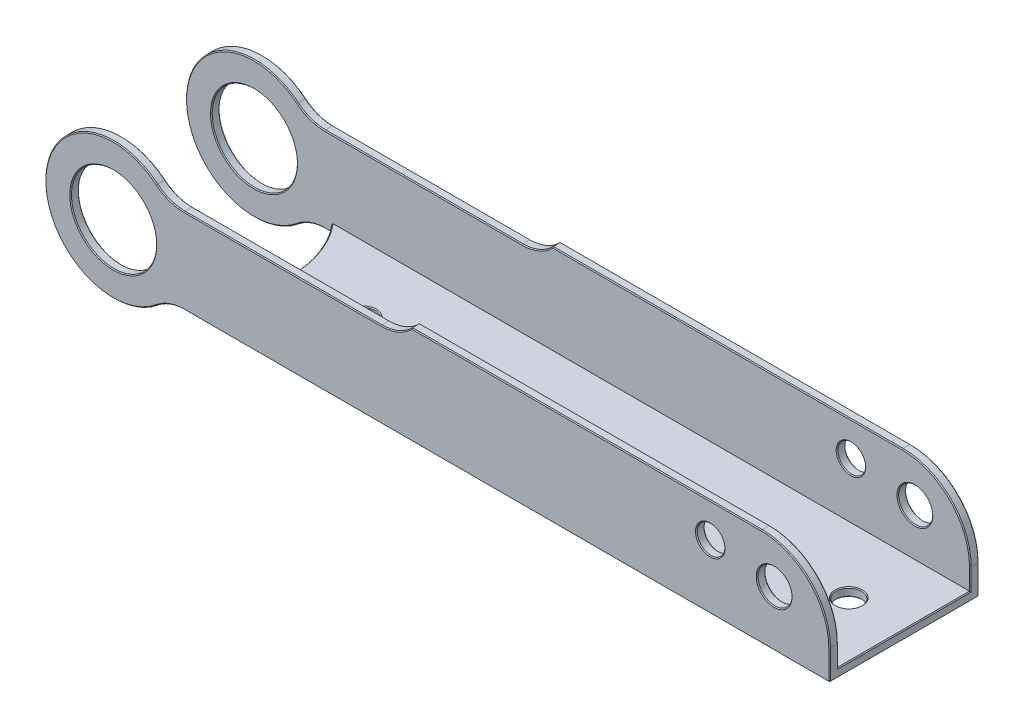
SolidWorks part; units mm, degrees
ref_plane "正面" through (0, 0, 0) normal (0, 0, 1) x (1, 0, 0)
ref_plane "平面" through (0, 0, 0) normal (0, 1, 0) x (1, 0, 0)
ref_plane "右側面" through (0, 0, 0) normal (1, 0, 0) x (0, 0, -1)
sketch "ArmA-L" plane through (0, 0, 0) normal (0, 0, 1) x (1, 0, 0)
  line L1 (12.49, 10) -> (70, 10)
  line L3 (12.49, -10) -> (168, -10)
  line L6 (70, 10) -> (70, 13)
  line L7 (70, 13) -> (168, 13)
  line L8 (168, -10) -> (168, 13)
  arc A0 (12.49, 10) -> (12.49, -10) centre (0, 0) ccw
  point P6 (70, 11.5)
  dimension "D2" = 32
  dimension "D1" = 70
  dimension "D3" = 168
  dimension "D4" = 3
  dimension "D5" = 10
extrude "ArmA-W" add sketch "ArmA-L" along normal mid plane 35
fillet "ﾌｨﾚｯﾄ1" radius 16 1 edges at (168, 13, 0)
fillet "ﾌｨﾚｯﾄ2" radius 10 3 edges at (12.49, -10, 0) (12.49, 10, 0) (70, 10, 0)
sketch "ｽｹｯﾁ2" plane through (0, 0, 17.5) normal (0, 0, 1) x (1, 0, 0)
  circle A0 centre (0, 0) radius 10
  dimension "D1" = 20
extrude "ｶｯﾄ - 押し出し1" cut sketch "ｽｹｯﾁ2" against normal through all
sketch "ｽｹｯﾁ3" plane through (0, 0, 0) normal (0, 1, 0) x (1, 0, 0)
  line L5 (-16, 15.5) -> (-16, -15.5)
  line L6 (-16, -15.5) -> (18.3235, -15.5)
  line L7 (-16, 15.5) -> (18.3235, 15.5)
  line L8 (-16, -17.5) -> (10.2235, -17.5) construction
  arc A0 (18.3235, 15.5) -> (18.3235, -15.5) centre (0, 0) cw
  point P10 (-16, 0)
  dimension "D3" = 24
  dimension "D1" = 2
extrude "ｶｯﾄ - 押し出し2" cut sketch "ｽｹｯﾁ3" against normal through all both and the other way through all
sketch "ArmA-t" plane through (0, 0, 0) normal (1, 0, 0) x (0, 0, -1)
  line L0 (-17.5, 13) -> (17.5, 13) construction
  line L1 (-15.5, -8) -> (15.5, -8)
  line L2 (-15.5, -8) -> (-15.5, 13)
  line L3 (-15.5, 13) -> (15.5, 13)
  line L4 (15.5, -8) -> (15.5, 13)
  line L5 (-17.5, -10) -> (17.5, -10) construction
  line L6 (15.5, 16) -> (15.5, -16) construction
  line L7 (-15.5, -16) -> (-15.5, 16) construction
  dimension "D1" = 2
extrude "ｶｯﾄ - 押し出し3" cut sketch "ArmA-t" along normal through all
sketch "ｽｹｯﾁ5" plane through (0, 0, 17.5) normal (0, 0, 1) x (1, 0, 0)
  line L0 (16.6132, -10) -> (168, -10) construction
  line L2 (168, -10) -> (168, -3) construction
  circle A0 centre (155, 3) radius 4
  circle A1 centre (140, 5) radius 3.25
  dimension "D1" = 8
  dimension "D2" = 6.5
  dimension "D4" = 15
  dimension "D3" = 13
  dimension "D5" = 13
  dimension "D6" = 28
extrude "ｶｯﾄ - 押し出し4" cut sketch "ｽｹｯﾁ5" against normal through all
sketch "ｽｹｯﾁ6" plane through (0, -10, 0) normal (0, -1, 0) x (1, 0, 0)
  line L0 (168, 17.5) -> (168, -17.5) construction
  circle A0 centre (155, 0) radius 3
  circle A1 centre (41, 0) radius 3
  dimension "D1" = 6
  dimension "D2" = 6
  dimension "D3" = 13
  dimension "D4" = 127
extrude "ｶｯﾄ - 押し出し5" cut sketch "ｽｹｯﾁ6" against normal up to next
chamfer "面取り1" distance 0.2 angle 45 56 edges at (155, -10, -3) (155, -8, 3) (41, -10, -3) (41, -8, 3) (168, -8, 0) (168, -10, 0) (159, 3, 15.5) (159, 3, 17.5) (143.25, 5, 15.5) (143.25, 5, 17.5) (151, 3, -15.5) (159, 3, -17.5) (136.75, 5, -15.5) (143.25, 5, -17.5) (168, -5.5, -15.5) (163.3137, 8.3137, -15.5) (111, 13, -15.5) (17.4684, -10, -15.5) (13.2164, -10.5946, -15.5) (-16, 0, -15.5) (13.2164, 10.5946, -15.5) (66.7316, 10.7805, -15.5) (39.7359, 10, -15.5) (17.4684, -10, 15.5) (13.2164, -10.5946, 15.5) (-16, 0, 15.5) (66.7316, 10.7805, 15.5) (13.2164, 10.5946, 15.5) (39.7359, 10, 15.5) (168, -5.5, 15.5) (163.3137, 8.3137, 15.5) (111, 13, 15.5) (-10, 0, -15.5) (10, 0, 15.5) (10, 0, 17.5) (92.3066, -10, 17.5) (13.2164, -10.5946, 17.5) (-16, 0, 17.5) (66.7316, 10.7805, 17.5) (13.2164, 10.5946, 17.5) (39.7359, 10, 17.5) (168, -6.5, 17.5) (111, 13, 17.5) (163.3137, 8.3137, 17.5) (10, 0, -17.5) (92.3066, -10, -17.5) (13.2164, -10.5946, -17.5) (-16, 0, -17.5) (66.7316, 10.7805, -17.5) (13.2164, 10.5946, -17.5) (39.7359, 10, -17.5) (168, -6.5, -17.5) (163.3137, 8.3137, -17.5) (111, 13, -17.5) (24, -8, 0) (24, -10, 0)
